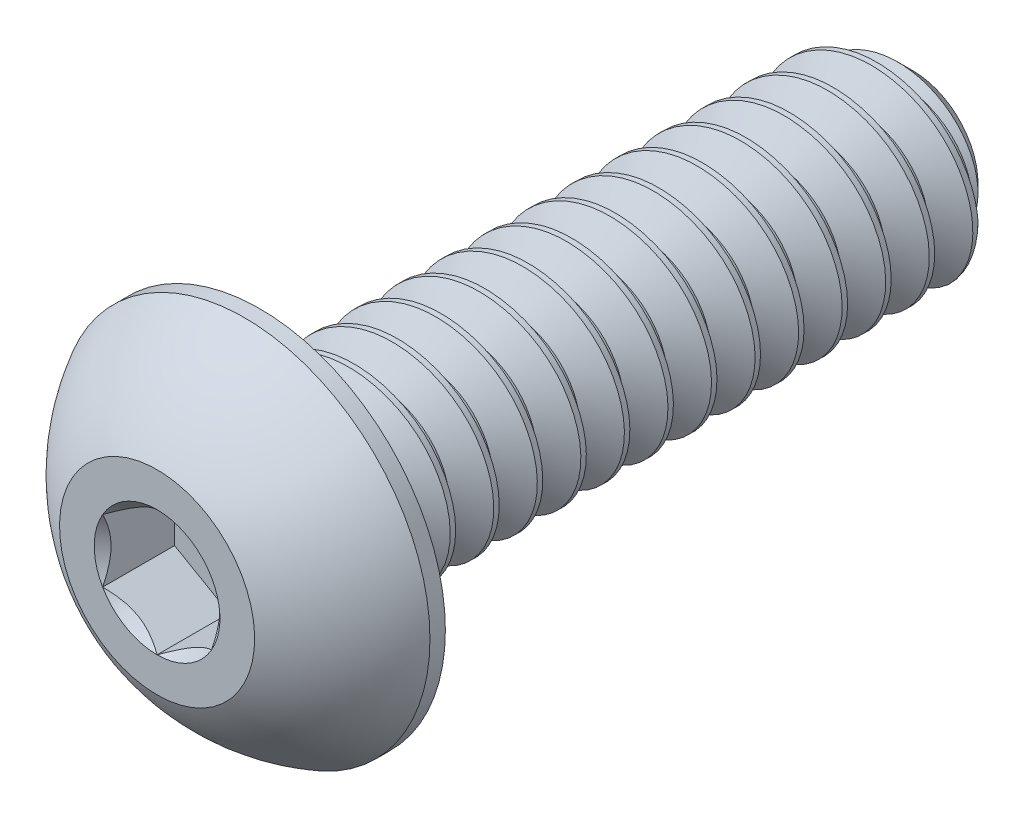
SolidWorks part; units mm, degrees
ref_plane "Front" through (0, 0, 0) normal (0, 0, 1) x (1, 0, 0)
ref_plane "Top" through (0, 0, 0) normal (0, 1, 0) x (1, 0, 0)
ref_plane "Right" through (0, 0, 0) normal (1, 0, 0) x (0, 0, -1)
sketch "Sketch1" plane through (0, 0, 0) normal (1, 0, 0) x (0, 0, -1)
  line L2 (1.4986, 1.4224) -> (11.0236, 1.4224)
  line L3 (11.0236, 1.4224) -> (11.0236, 0)
  line L4 (11.0236, 0) -> (1.4986, 0)
  line L6 (1.2738, 2.7051) -> (1.4986, 2.7051) construction
  line L7 (11.0236, 1.4224) -> (11.0236, -1.4224) construction
  line L8 (0, 0) -> (1.4986, 0) construction
  line L9 (1.4986, 2.7051) -> (1.4986, -2.7051) construction
  line L11 (1.4986, 1.4224) -> (1.4986, 0)
  line L13 (0, 0.7937) -> (0, -0.7937) construction
  line L14 (0, 0.7937) -> (0, 1.4224) construction
  arc A3 (0, 1.4224) -> (1.2738, 2.7051) centre (2.7151, 0) cw construction
  dimension "D1" = 0.2248
  dimension "Head Ht" = 1.4986
  dimension "Head Dia" = 5.4102
  dimension "Dia" = 2.8448
  dimension "Lg" = 9.525
  dimension "Hex" = 1.5875
revolve "Revolve1" add sketch "Sketch1" angle 360 mid plane about L4
sketch "Sketch3" plane through (0, 0, -11.0236) normal (0, 0, -1) x (-1, 0, 0)
  circle A0 centre (0, 0) radius 1.4224
curve "Helix/Spiral1" pitch 0.635 height 10.16 radius 1.4224 centre (0, 0, -11.0236) axis (0, 0, 1) start towards (0, 1, 0)
sketch "Sketch2" plane through (0, 0, 0) normal (1, 0, 0) x (0, 0, -1)
  line L0 (11.0236, 1.4224) -> (11.5792, 1.4224)
  line L1 (11.5792, 1.4224) -> (11.3411, 1.01)
  line L2 (11.3411, 1.01) -> (11.2617, 1.01)
  line L3 (11.2617, 1.01) -> (11.0236, 1.4224)
  line L4 (11.1427, 1.2162) -> (11.4602, 1.2162) construction
  dimension "D1" = 60
  dimension "D2" = 0.0794
  dimension "D3" = 0.3175
chamfer "Chamfer1" distance 0.4763 angle 45 1 edges at (0, 1.4224, -11.0236)
sweep "Cut-Sweep1" cut profiles "Sketch2" path "Helix/Spiral1"
sketch "Sketch7" plane through (0, 0, 0) normal (1, 0, 0) x (0, 0, -1)
  line L6 (1.2738, 2.7051) -> (1.4986, 2.7051) construction
  line L8 (0, 0) -> (1.4986, 0) construction
  line L11 (1.4986, 2.7051) -> (1.4986, -2.7051) construction
  line L12 (1.2738, 2.7051) -> (1.4986, 2.7051)
  line L13 (0, 0) -> (1.4986, 0)
  line L14 (0, 0.7937) -> (0, -0.7937) construction
  line L15 (1.4986, 2.7051) -> (1.4986, 0)
  line L16 (0, 1.4224) -> (0, 0)
  arc A2 (1.2738, 2.7051) -> (0, 1.4224) centre (2.7151, 0) ccw construction
  arc A3 (1.2738, 2.7051) -> (0, 1.4224) centre (2.7151, 0) ccw
revolve "Revolve2" add sketch "Sketch7" angle 360 mid plane about L13
sketch "Sketch5" plane through (0, 0, 0) normal (0, 0, 1) x (1, 0, 0)
  line L1 (0.7937, -0.4583) -> (0.7937, 0.4583)
  line L2 (0.7937, 0.4583) -> (0, 0.9165)
  line L3 (0, 0.9165) -> (-0.7937, 0.4583)
  line L4 (-0.7937, 0.4583) -> (-0.7937, -0.4583)
  line L5 (-0.7937, -0.4583) -> (0, -0.9165)
  line L6 (0, -0.9165) -> (0.7937, -0.4583)
  circle A0 centre (0, 0) radius 0.7937 construction
extrude "Cut-Extrude2" cut sketch "Sketch5" against normal blind 1.049
sketch "Sketch6" plane through (0, 0, 0) normal (0, 0, 1) x (1, 0, 0)
  circle A0 centre (0, 0) radius 0.9165
extrude "Cut-Extrude3" cut sketch "Sketch6" against normal blind 1.049 draft 45
sketch "Sketch9" [suppressed] plane through (0, 0, -1.4986) normal (0, 0, 1) x (1, 0, 0)
  circle A2 centre (0, 0) radius 1.4224
extrude "Boss-Extrude2" [suppressed] add sketch "Sketch9" against normal offset from surface (12.7 mm away) 31.75 up to face at (0, 0.9461, -11.0236)
sketch "Sketch10" plane through (0, 0, 0) normal (1, 0, 0) x (0, 0, -1)
  line L0 (11.0236, 1.4224) -> (11.0236, -1.4224) construction
  point P0 (10.0711, -1.4224)
  dimension "D1" = 0.9525
equation "\"D3@Helix/Spiral1\" = \"Lg@Sketch1\" + \"D4@Helix/Spiral1\""
equation "\"D2@Sketch2\" = \"D4@Helix/Spiral1\" * .125"
equation "\"D3@Sketch2\" = \"D4@Helix/Spiral1\" * .5"
equation "\"D1@Chamfer1\" = \"D4@Helix/Spiral1\" * .75"
equation "\"D1@Cut-Extrude2\" = \"Head Ht@Sketch1\" * .7"
equation "\"D1@Sketch1\" = \"Head Ht@Sketch1\" * .15"
equation "\"D1@Sketch10\" = \"D4@Helix/Spiral1\" * 1.5"
equation "\"D1@Cut-Extrude3\" = \"D1@Cut-Extrude2\""
